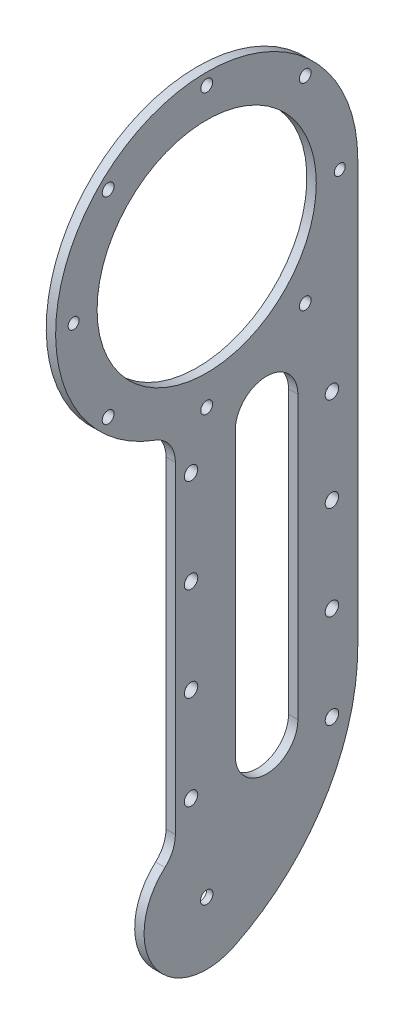
SolidWorks part; units mm, degrees
ref_plane "前视基准面" through (0, 0, 0) normal (0, 0, 1) x (1, 0, 0)
ref_plane "上视基准面" through (0, 0, 0) normal (0, 1, 0) x (1, 0, 0)
ref_plane "右视基准面" through (0, 0, 0) normal (1, 0, 0) x (0, 0, -1)
sketch "草图1" plane through (0, 0, 0) normal (1, 0, 0) x (0, 0, -1)
  line L0 (0, -180) -> (0, 0) construction
  line L5 (47.4197, -8.9128) -> (14.7419, -182.7708)
  line L7 (-14.7419, -182.7708) -> (-47.4197, -8.9128)
  arc A21 (47.4197, -8.9128) -> (-47.4197, -8.9128) centre (0, 0) ccw
  circle A56 centre (0, -180) radius 15
  dimension "D1" = 180
  dimension "D2" = 30
  dimension "D3" = 48.25
extrude "凸台-拉伸3" add sketch "草图1" along normal blind 3 contours A56 L5 A21 L7 | A56 region at (0, -48.6265, 0) region at (0, -180, 0)
sketch "草图5" plane through (0, 0, 0) normal (1, 0, 0) x (0, 0, -1)
  line L0 (0, 0) -> (0, 44.5) construction
  line L1 (-42.5, 0) -> (0, 0) construction
  circle A1 centre (0, 44.5) radius 1.9
  circle A2 centre (31.4663, 31.4663) radius 1.9
  circle A3 centre (44.5, 0) radius 1.9 construction
  circle A4 centre (31.4663, -31.4663) radius 1.9
  circle A5 centre (0, -44.5) radius 1.9
  circle A6 centre (-31.4663, -31.4663) radius 1.9
  circle A7 centre (-44.5, 0) radius 1.9 construction
  circle A8 centre (-31.4663, 31.4663) radius 1.9
  circle A9 centre (-42.5, 0) radius 1.75
  circle A11 centre (42.5, 0) radius 1.75
  point P22 (0, 0)
  dimension "D2" = 3.8
  dimension "D4" = 3.5
  dimension "D5" = 85
  dimension "D1" = 44.5
  dimension "D3" = 8
extrude "切除-拉伸3" cut sketch "草图5" along normal through all
sketch "草图6" plane through (3, 0, 0) normal (1, 0, 0) x (0, 0, -1)
  circle A0 centre (0, -180) radius 2
  dimension "D1" = 4
extrude "切除-拉伸4" cut sketch "草图6" against normal blind 10
sketch "草图7" plane through (3, 0, 0) normal (1, 0, 0) x (0, 0, -1)
  line L0 (48.25, 0) -> (48.25, -134.8483)
  line L1 (-10, -162.6795) -> (-10, -47.2024)
  line L4 (0, -180) -> (0, -91.0566) construction
  circle A0 centre (0, -180) radius 20
  circle A2 centre (0, 0) radius 48.25
  arc A4 (8.7467, -197.9859) -> (48.25, -134.8483) centre (-21.9577, -134.8483) ccw
  point P2 (0, 0)
  circle M2 centre (0, -180) radius 2
  circle M3 centre (-42.5, 0) radius 1.75
  circle M4 centre (-31.4663, 31.4663) radius 1.9
  circle M5 centre (-31.4663, -31.4663) radius 1.9
  circle M6 centre (0, -44.5) radius 1.9
  circle M7 centre (0, 44.5) radius 1.9
  circle M8 centre (42.5, 0) radius 1.75
  circle M9 centre (31.4663, 31.4663) radius 1.9
  circle M10 centre (31.4663, -31.4663) radius 1.9
  line M11 (-47.4197, -8.9128) -> (-14.7419, -182.7708)
  arc M12 (-14.7419, -182.7708) -> (14.7419, -182.7708) centre (0, -180) ccw
  line M13 (14.7419, -182.7708) -> (47.4197, -8.9128)
  arc M14 (47.4197, -8.9128) -> (-47.4197, -8.9128) centre (0, 0) ccw
  dimension "D1" = 96.5
  dimension "D3" = 40
  dimension "D2" = 10
extrude "切除-拉伸5" cut sketch "草图7" against normal blind 10 flip side to cut contours A0 M13 M12 M11 | A0 M2 M11 M12 M13 | A2 L1 A0 M13 | A2 M14 M3 M5 M7 M9 M10 M8 M6 M4 region at (3, 0, 0) region at (3, -96.0689, -11.7324) region at (3, -193.1943, 14.3564) region at (3, -176.8553, 0)
extrude "凸台-拉伸6" add sketch "草图7<3>" against normal blind 3 contours L0 A0 M13 | A0 M11 M13 M12 | A0 M13 M11 M12 M2 region at (3, -118.9605, -36.437) region at (3, -193.1943, 14.3564) region at (3, -176.8553, 0)
sketch "草图7<3>" plane through (3, 0, 0) normal (1, 0, 0) x (0, 0, -1) same geometry as "草图7"
fillet "圆角1" radius 10 2 edges at (1.5, -162.6795, 10) (1.5, -47.2024, 10)
sketch "草图9" plane through (3, 0, 0) normal (1, 0, 0) x (0, 0, -1)
  line L0 (0, 0) -> (40, 0) construction
  line L1 (40, 0) -> (40, -117.8175) construction
  line L4 (-5, -60.1455) -> (40, -60.1455) construction
  circle A0 centre (40, -60.1455) radius 2.15
  circle A1 centre (-5, -60.1455) radius 2.15
  point P3 (0, 0)
  dimension "D2" = 4.3
  dimension "D3" = 4.3
  dimension "D1" = 40
  dimension "D4" = 45
extrude "切除-拉伸6" cut sketch "草图9" against normal blind 3
pattern_linear "阵列(线性)1" count 4 spacing 30 along (0, -1, 0) of "切除-拉伸6"
sketch "草图10" plane through (0, 0, 0) normal (-1, 0, 0) x (0, 0, 1)
  circle A0 centre (0, -180) radius 5
  dimension "D1" = 10
extrude "切除-拉伸7" cut sketch "草图10" against normal blind 1
sketch "草图11" plane through (0, 0, 0) normal (-1, 0, 0) x (0, 0, 1)
  circle A0 centre (0, 0) radius 35
  dimension "D1" = 70
extrude "切除-拉伸8" cut sketch "草图11" against normal blind 7
sketch "草图12" plane through (0, 0, 0) normal (-1, 0, 0) x (0, 0, 1)
  line L0 (-48.25, -100.453) -> (10, -100.453) construction
  line L7 (-48.25, 0) -> (-48.25, -134.8483) construction
  line L8 (10, -157.6393) -> (10, -54.7089) construction
  line L15 (-19.125, -145.453) -> (-19.125, -55.453) construction
  line L16 (-29.125, -145.453) -> (-29.125, -55.453)
  line L17 (-9.125, -145.453) -> (-9.125, -55.453)
  arc A11 (-29.125, -145.453) -> (-9.125, -145.453) centre (-19.125, -145.453) ccw
  arc A12 (-9.125, -55.453) -> (-29.125, -55.453) centre (-19.125, -55.453) ccw
  point P2 (-19.125, -100.453)
  dimension "D1" = 20
  dimension "D2" = 90
extrude "切除-拉伸9" cut sketch "草图12" against normal blind 7
